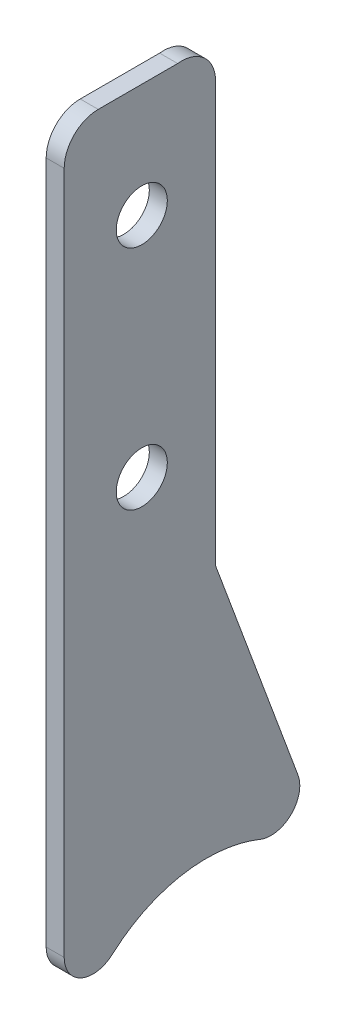
SolidWorks part; units mm, degrees
material "ASTM A36 Steel"
ref_plane "X-Y Datum" through (0, 0, 0) normal (0, 0, 1) x (1, 0, 0)
ref_plane "X-Z Datum" through (0, 0, 0) normal (0, 1, 0) x (1, 0, 0)
ref_plane "Y-Z Datum" through (0, 0, 0) normal (1, 0, 0) x (0, 0, -1)
sketch "Sketch1" plane through (0, 0, 0) normal (1, 0, 0) x (0, 0, -1)
  line L4 (530.2175, 94.5021) -> (541.5105, 64.0269)
  line L5 (516.8775, 94.5021) -> (516.8775, 59.7816)
  line L8 (530.2175, 94.5021) -> (530.2175, 131.5021)
  line L9 (526.8775, 134.5021) -> (519.8775, 134.5021)
  line L10 (516.8775, 131.5021) -> (516.8775, 94.5021)
  line L11 (516.8775, 94.5021) -> (530.2175, 94.5021) construction
  arc A4 (530.2175, 131.5021) -> (526.8775, 134.5021) centre (527.2176, 131.5215) ccw
  arc A5 (519.8775, 134.5021) -> (516.8775, 131.5021) centre (519.8775, 131.5021) ccw
  circle A6 centre (523.7175, 104.5021) radius 3.025
  circle A7 centre (523.7175, 124.5021) radius 3.025
  spline S1 degree 3 poles (525.4949, 71.9358) (549.5915, 79.968) (557.8191, 55.2852) (533.7225, 47.2531) (509.626, 39.2209) (501.3984, 63.9036) (525.4949, 71.9358) (549.5915, 79.968) (557.8191, 55.2852) knots -0.5 0 0 0 0.5 0.5 0.5 1 1 1 1.5 1.5 1.5 weights 1 0.333333 0.333333 1 0.333333 0.333333 1 0.333333 0.333333 only from (525.4949, 71.9358) to (525.4949, 71.9358)
extrude "Boss-Extrude1" add sketch "Sketch1" along normal blind 1.5875 contours L11 L5 S1 L4 | L10 L11 L8 A4 L9 A5 A6 A7 | A6 | A7 region at (0, 114.3466, -523.5275) region at (0, 81.2428, -525.6451) region at (0, 104.5021, -523.7175) region at (0, 124.5021, -523.7175)
fillet "Fillet1" radius 2.54 2 edges at (0.7937, 59.7816, -516.8775) (0.7937, 64.0269, -541.5105)
hole_wizard "M4 Clearance Hole1" positions "Sketch2" profile "Sketch3" hole size "M4" standard "ANSI Metric" end condition through all
sketch "Sketch2" plane through (1.5875, 0, 0) normal (1, 0, 0) x (0, 0, -1)
  point P0 (523.7175, 124.5021)
  point P2 (523.7175, 104.5021)
sketch "Sketch3" plane through (1.5875, 124.5021, -523.7175) normal (0, 1, 0) x (0, 0, -1)
  line L0 (0, 0) -> (0, 1.5875)
  line L1 (0, 1.5875) -> (2.25, 1.5875)
  line L2 (2.25, 1.5875) -> (2.25, 0)
  line L5 (2.25, 0) -> (0, 0)
  line L11 (0, -6.35) -> (0, 107.95) construction
  dimension "Thru Hole Dia." = 4.5
  dimension "Thru Hole Depth" = 1.5875
